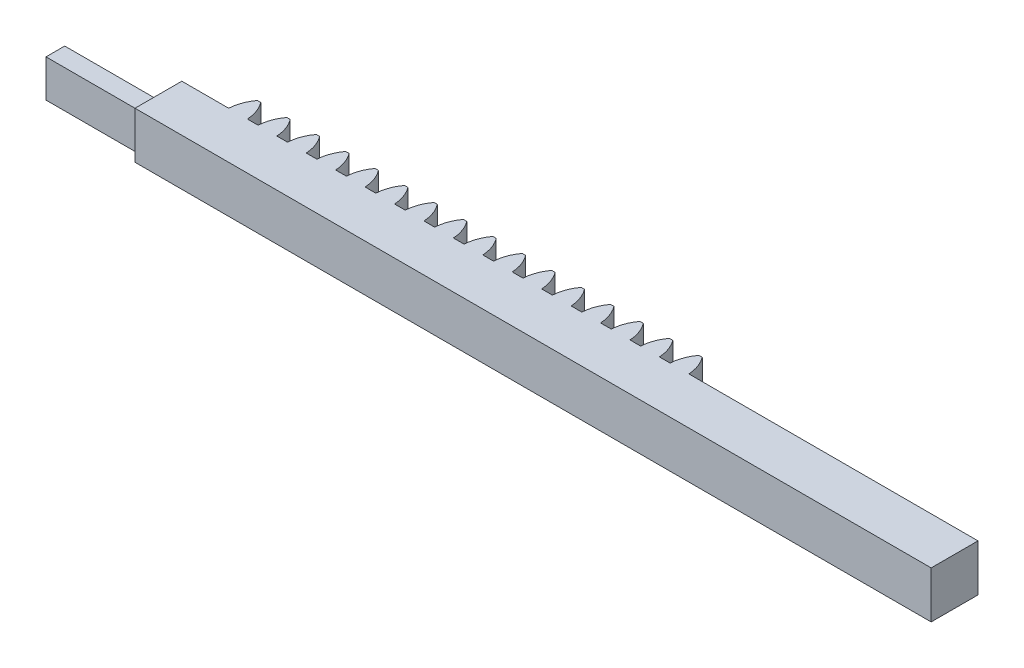
SolidWorks part; units mm, degrees
ref_plane "Front Plane" through (0, 0, 0) normal (0, 0, 1) x (1, 0, 0)
ref_plane "Top Plane" through (0, 0, 0) normal (0, 1, 0) x (1, 0, 0)
ref_plane "Right Plane" through (0, 0, 0) normal (1, 0, 0) x (0, 0, -1)
sketch "Sketch2" plane through (0, 0, 0) normal (0, 1, 0) x (1, 0, 0)
  line L0 (-32.7528, 0) -> (52.2472, 0)
  line L1 (52.2472, 0) -> (52.2472, 5)
  line L2 (52.2472, 5) -> (-32.7528, 5)
  line L3 (-32.7528, 5) -> (-32.7528, 0)
  line L4 (-27.7528, 5) -> (-27.7528, 8.2168) construction
  line L5 (47.2472, 5) -> (47.2472, 8.2384) construction
  line L6 (-26.9339, 7.25) -> (-26.5717, 7.25)
  line L7 (-26.7528, 7.25) -> (-26.7528, 4.3153) construction
  line L8 (-27.7528, 5) -> (-26.9339, 7.25) construction
  arc A0 (-27.7528, 5) -> (-26.9339, 7.25) centre (-23.6412, 4.7775) cw
  arc A1 (-25.7528, 5) -> (-26.5717, 7.25) centre (-29.8644, 4.7775) ccw
  dimension "D1" = 85
  dimension "D2" = 5
  dimension "D3" = 5
  dimension "D4" = 5
  dimension "D5" = 1
  dimension "D6" = 20
  dimension "D7" = 2.25
extrude "Boss-Extrude1" add sketch "Sketch2" along normal blind 5 contours L2 L3 L0 L1 region at (9.7472, 0, -2.5)
extrude "Boss-Extrude2" add sketch "Sketch2<3>" along normal blind 5 contours L2 A1 L6 A0 region at (-26.7528, 0, -5.9152)
sketch "Sketch2<3>" plane through (0, 0, 0) normal (0, 1, 0) x (1, 0, 0) same geometry as "Sketch2"
pattern_linear "LPattern1" count 16 spacing 3.142 along (1, 0, 0) of "Boss-Extrude2"
sketch "Sketch3" plane through (-32.7528, 0, 0) normal (-1, 0, 0) x (0, 0, 1)
  line L0 (-2.5, 4.5) -> (-2.5, 0.5)
  line L1 (-2.5, 0.5) -> (-0.5, 0.5)
  line L2 (-0.5, 0.5) -> (-0.5, 4.5)
  line L3 (-0.5, 4.5) -> (-2.5, 4.5)
  line L4 (-5, 5) -> (0, 5) construction
  line L5 (0, 5) -> (0, 0) construction
  dimension "D1" = 2
  dimension "D2" = 4
  dimension "D3" = 0.5
  dimension "D4" = 0.5
extrude "Boss-Extrude3" add sketch "Sketch3" along normal blind 10
